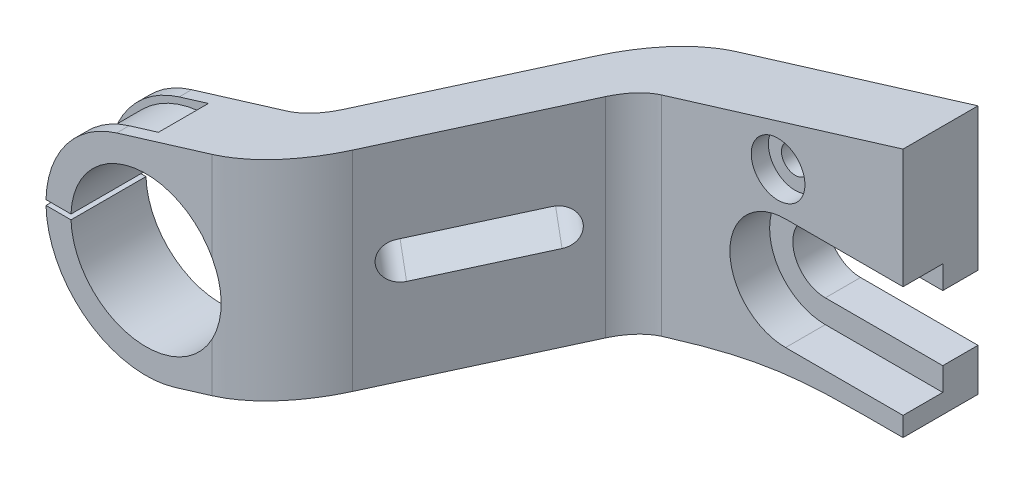
SolidWorks part; units mm, degrees
ref_plane "Front" through (0, 0, 0) normal (0, 0, 1) x (1, 0, 0)
ref_plane "Top" through (0, 0, 0) normal (0, 1, 0) x (1, 0, 0)
ref_plane "Right" through (0, 0, 0) normal (1, 0, 0) x (0, 0, -1)
sketch "Sketch1" plane through (0, 0, 0) normal (0, 1, 0) x (1, 0, 0)
  line L0 (0, 0) -> (-96.6846, 0)
  line L1 (-134.9868, -17.8606) -> (-181.1332, -72.8558)
  line L2 (-196.4541, -80) -> (-280, -80)
  arc A0 (-96.6846, 0) -> (-134.9868, -17.8606) centre (-96.6846, -50) ccw
  arc A1 (-181.1332, -72.8558) -> (-196.4541, -80) centre (-196.4541, -60) cw
  point P3 (-200.1648, -80)
  point P6 (0, 0)
  point P9 (-120, 0)
  dimension "D1" = 120
  dimension "D4" = 50
  dimension "D5" = 20
  dimension "D2" = 80
  dimension "D3" = 280
  dimension "D6" = 50
extrude "Extrude-Thin1" add sketch "Sketch1" against normal blind 150 thin thin type one direction reverse wall 30
sketch "Sketch2" plane through (0, 0, 0) normal (0, 0, 1) x (1, 0, 0)
  line L0 (0, 0) -> (-234.6765, -71.7478)
  line L2 (0, -150) -> (0, 0) construction
  line L3 (0, -100) -> (0, 0)
  line L4 (0, 0) -> (-96.6846, 0) construction
  line L5 (-196.4541, -150) -> (-280, -150) construction
  line L6 (-211.2868, -148.2522) -> (-95, -112.6998)
  line L7 (44.3467, -100) -> (-44.3467, -100) construction
  line L8 (-55.2954, -100.5608) -> (-134.1815, -124.6787) construction
  arc A0 (-234.6765, -71.7478) -> (-211.2868, -148.2522) centre (-222.9816, -110) ccw
  spline S0 degree 3 poles (-95, -112.6998) (-51.5325, -99.4104) (-36.9555, -100) (0, -100) knots 0 0 0 0 1 1 1 1
  dimension "D2" = 40
  dimension "D1" = 17
  dimension "D3" = 100
  dimension "D4" = 95
extrude "Cut-Extrude1" cut sketch "Sketch2" along normal through all flip side to cut
sketch "Sketch3" plane through (0, 0, 110) normal (0, 0, 1) x (1, 0, 0)
  circle A0 centre (-222.9816, -110) radius 30
  dimension "D1" = 60
extrude "Cut-Extrude2" cut sketch "Sketch3" against normal through all
sketch "Sketch4" plane through (0, 0, 110) normal (0, 0, 1) x (1, 0, 0)
  line L0 (-222.9816, -68.1723) -> (-222.9816, -72.5)
  line L1 (-196.4541, -60.0621) -> (-234.6765, -71.7478) construction
  line L2 (-234.6765, -71.7478) -> (-222.9816, -68.1723)
  line L3 (-222.9816, -147.5) -> (-222.9816, -150)
  arc A0 (-234.6765, -71.7478) -> (-211.2868, -148.2522) centre (-222.9816, -110) ccw construction
  arc A1 (-234.6765, -71.7478) -> (-222.9816, -150) centre (-222.9816, -110) ccw
  arc A2 (-222.9816, -72.5) -> (-222.9816, -147.5) centre (-222.9816, -110) ccw
  dimension "D1" = 2.5
extrude "Cut-Extrude3" cut sketch "Sketch4" against normal mid plane 20 from offset 15 offset against normal yes
sketch "Sketch5" plane through (0, 0, 110) normal (0, 0, 1) x (1, 0, 0)
  line L5 (-322.9816, -109) -> (-222.9816, -109)
  line L6 (-322.9816, -109) -> (-322.9816, -111)
  line L7 (-322.9816, -111) -> (-222.9816, -111)
  line L8 (-222.9816, -109) -> (-222.9816, -111)
  dimension "D1" = 2
  dimension "D2" = 100
extrude "Cut-Extrude4" cut sketch "Sketch5" against normal through all
hole_wizard "CBORE SLOT for M24 Hex Head Bolt1" positions "Sketch6" profile "Sketch7" size "M24" standard "ANSI Metric" slot yes end condition through all
sketch "Sketch6" plane through (0, 0, 30) normal (0, 0, 1) x (1, 0, 0)
  line L0 (0, -100) -> (0, 0) construction
  line L1 (-60, -70) -> (60, -70) construction
  point P10 (0, -70)
  dimension "D1" = 120
  dimension "D2" = 30
sketch "Sketch7" plane through (0, -70, 30) normal (1, 0, 0) x (0, -1, 0)
  line L0 (0, 0) -> (0, 30)
  line L1 (0, 30) -> (13, 30)
  line L3 (13, 30) -> (13, 15.9)
  line L4 (13, 15.9) -> (22.285, 15.9)
  line L5 (22.285, 15.9) -> (22.285, 0)
  line L7 (22.285, 0) -> (0, 0)
  line L11 (0, -6.35) -> (0, 107.95) construction
  dimension "Thru Hole Dia." = 26
  dimension "Thru Hole Depth" = 30
  dimension "C'Bore Dia." = 44.57
  dimension "C'Bore Depth" = 15.9
hole_wizard "CBORE for M10 Hex Head Bolt1" positions "Sketch9" profile "Sketch10" counterbore size "M10" standard "ANSI Metric" end condition through all
sketch "Sketch9" plane through (0, 0, 30) normal (0, 0, 1) x (1, 0, 0)
  line L0 (0, -47.715) -> (0, 0) construction
  point P0 (-50, -32)
  dimension "D1" = 50
  dimension "D2" = 32
sketch "Sketch10" plane through (-50, -32, 30) normal (1, 0, 0) x (0, -1, 0)
  line L0 (0, 0) -> (0, 30)
  line L1 (0, 30) -> (5.5, 30)
  line L3 (5.5, 30) -> (5.5, 6.85)
  line L4 (5.5, 6.85) -> (10.74, 6.85)
  line L5 (10.74, 6.85) -> (10.74, 0)
  line L7 (10.74, 0) -> (0, 0)
  line L11 (0, -6.35) -> (0, 107.95) construction
  dimension "Thru Hole Dia." = 11
  dimension "Thru Hole Depth" = 30
  dimension "C'Bore Dia." = 21.48
  dimension "C'Bore Depth" = 6.85
sketch "Sketch11" plane through (-47.4376, 0, -39.8048) normal (0.766, 0, 0.6428) x (0.6428, 0, -0.766)
  line L0 (-158.3426, -87.4483) -> (-114.1871, -78.7708) construction
  line L1 (-159.7888, -80.089) -> (-115.6334, -71.4116)
  line L2 (-156.8963, -94.8075) -> (-112.7409, -86.1301)
  line L3 (-100.4499, -34.2435) -> (-172.2409, -48.3519) construction
  line L4 (-114.1871, -78.7708) -> (-100.4499, -76.0712) construction
  line L5 (-100.4499, -117.8989) -> (-100.4499, -34.2435) construction
  arc A0 (-159.7888, -80.089) -> (-156.8963, -94.8075) centre (-158.3426, -87.4483) ccw
  arc A1 (-112.7409, -86.1301) -> (-115.6334, -71.4116) centre (-114.1871, -78.7708) ccw
  point P2 (-136.2649, -83.1095)
  dimension "D1" = 45
  dimension "D2" = 15
  dimension "D3" = 36.5
extrude "Cut-Extrude5" cut sketch "Sketch11" against normal through all
